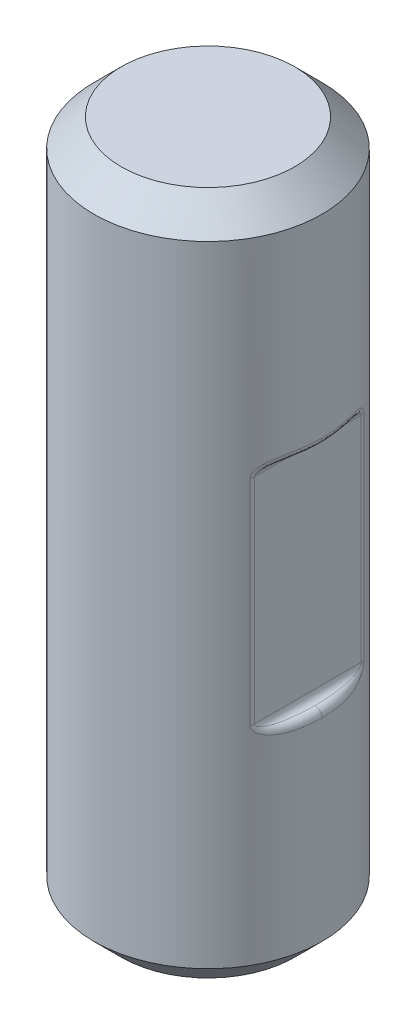
SolidWorks part; units mm, degrees
ref_plane "Front Plane" through (0, 0, 0) normal (0, 0, 1) x (1, 0, 0)
ref_plane "Top Plane" through (0, 0, 0) normal (0, 1, 0) x (1, 0, 0)
ref_plane "Right Plane" through (0, 0, 0) normal (1, 0, 0) x (0, 0, -1)
sketch "Sketch1" plane through (0, 0, 0) normal (0, 0, 1) x (1, 0, 0)
  line L0 (3.175, 9.525) -> (3.175, -9.525)
  line L1 (0, 5.0542) -> (0, -5.0542) construction
  line L2 (0, 9.525) -> (3.175, 9.525)
  line L3 (3.175, -9.525) -> (0, -9.525)
  line L4 (0, -9.525) -> (0, 9.525)
  point P3 (3.175, 0)
  dimension "D1" = 6.35
  dimension "D2" = 19.05
revolve "Revolve1" add sketch "Sketch1" angle 360 about L1
sketch "Sketch3" plane through (0, 0, 0) normal (0, 0, 1) x (1, 0, 0)
  line L0 (3.175, -9.525) -> (3.175, 9.525) construction
  line L1 (2.7781, 3.175) -> (3.175, 3.175)
  line L2 (2.7781, 3.175) -> (2.7781, -3.175)
  line L3 (2.7781, -3.175) -> (3.175, -3.175)
  line L4 (3.175, 3.175) -> (3.175, -3.175)
  point P4 (2.7781, 0)
  dimension "D1" = 0.3969
  dimension "D2" = 6.35
extrude "Cut-Extrude2" cut sketch "Sketch3" against normal through all both and the other way through all contours L4 L3 L2 L1
fillet "Fillet3" radius 0.1984 4 edges at (2.7781, 0, -1.5371) (2.7781, 0, 1.5371) (2.7781, -3.175, 0) (2.7781, 3.175, 0)
chamfer "Chamfer1" distance 0.762 angle 45 2 edges at (0, -9.525, 3.175) (0, 9.525, 3.175)
